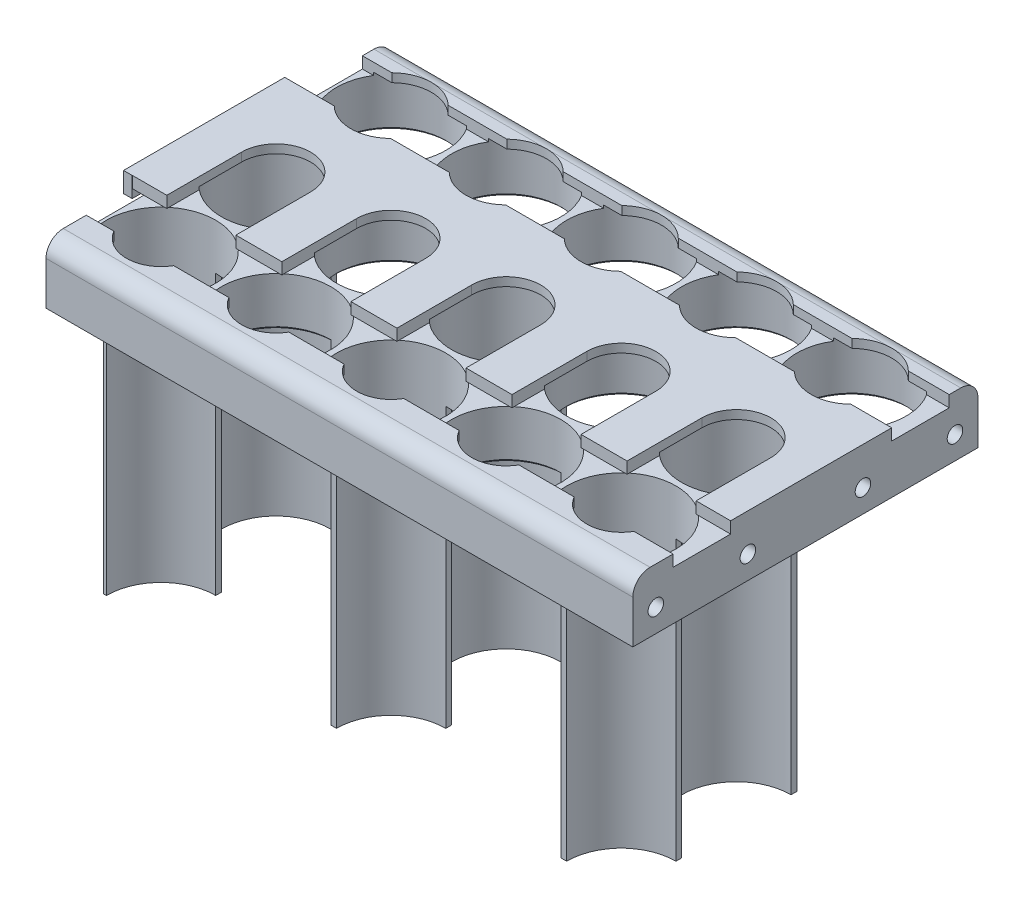
SolidWorks part; units mm, degrees
ref_plane "Front Plane" through (0, 0, 0) normal (0, 0, 1) x (1, 0, 0)
ref_plane "Top Plane" through (0, 0, 0) normal (0, 1, 0) x (1, 0, 0)
ref_plane "Right Plane" through (0, 0, 0) normal (1, 0, 0) x (0, 0, -1)
sketch "Sketch1" plane through (0, 0, 0) normal (0, 1, 0) x (1, 0, 0)
  line L0 (-48.3182, 0) -> (75.8679, 0)
  line L1 (-38.6124, 30) -> (61.3876, 30)
  line L2 (-38.6124, 30) -> (-38.6124, -30)
  line L3 (-38.6124, -30) -> (61.3876, -30)
  line L4 (61.3876, 30) -> (61.3876, -30)
  circle A0 centre (-28.6124, 20) radius 9.5
  circle A1 centre (-8.6124, 20) radius 9.5
  circle A2 centre (11.3876, 20) radius 9.5
  circle A3 centre (31.3876, 20) radius 9.5
  circle A4 centre (51.3876, 20) radius 9.5
  circle A5 centre (-28.6124, 0) radius 9.5
  circle A6 centre (-8.6124, 0) radius 9.5
  circle A7 centre (11.3876, 0) radius 9.5
  circle A8 centre (31.3876, 0) radius 9.5
  circle A9 centre (51.3876, 0) radius 9.5
  circle A10 centre (51.3876, -20) radius 9.5
  circle A11 centre (31.3876, -20) radius 9.5
  circle A12 centre (11.3876, -20) radius 9.5
  circle A13 centre (-8.6124, -20) radius 9.5
  circle A14 centre (-28.6124, -20) radius 9.5
  dimension "D3" = 19
  dimension "D4" = 19
  dimension "D5" = 19
  dimension "D6" = 19
  dimension "D7" = 19
  dimension "D8" = 20
  dimension "D9" = 20
  dimension "D10" = 20
  dimension "D11" = 20
  dimension "D12" = 10
  dimension "D13" = 10
  dimension "D14" = 20
  dimension "D15" = 20
  dimension "D16" = 20
  dimension "D17" = 20
  dimension "D18" = 20
  dimension "D19" = 10
  dimension "D20" = 20
  dimension "D21" = 20
  dimension "D22" = 20
  dimension "D23" = 20
  dimension "D25" = 30
  dimension "D26" = 19
  dimension "D27" = 19
  dimension "D28" = 19
  dimension "D29" = 19
  dimension "D30" = 19
  dimension "D1" = 60
  dimension "D2" = 100
  dimension "D24" = 10
extrude "Boss-Extrude1" add sketch "Sketch1" along normal blind 10 contours A9 L0 A8 A7 A6 A5 L2 L3 L4 A13 A11 A10 A12 A14 | A9 L0 L4 L1 L2 A5 A6 A7 A8 A4 A3 A2 A1 A0 region at (-37.5683, 0, -15) region at (-38.3624, 0, 1.044)
sketch "Sketch2" plane through (0, 10, 0) normal (0, 1, 0) x (1, 0, 0)
  line L1 (-38.6124, 30) -> (61.3876, 30)
  line L2 (-38.6124, 30) -> (-38.6124, -30)
  line L3 (-38.6124, -30) -> (61.3876, -30)
  line L4 (61.3876, 30) -> (61.3876, -30)
extrude "Boss-Extrude2" add sketch "Sketch2" against normal blind 1.5
sketch "Sketch3" plane through (0, 10, 0) normal (0, 1, 0) x (1, 0, 0)
  line L0 (-28.6124, 0) -> (-28.6124, -20) construction
  line L1 (-22.6124, 0) -> (-22.6124, -20)
  line L2 (-34.6124, 0) -> (-34.6124, -20)
  line L3 (-8.6124, 0) -> (-8.6124, -20) construction
  line L4 (-2.6124, 0) -> (-2.6124, -20)
  line L5 (-14.6124, 0) -> (-14.6124, -20)
  line L6 (11.3876, 34.8884) -> (11.3876, -40.3884)
  line L7 (61.3876, 30) -> (61.3876, -30) construction
  line L8 (31.3876, 0) -> (31.3876, -20) construction
  line L9 (25.3876, 0) -> (25.3876, -20)
  line L10 (37.3876, 0) -> (37.3876, -20)
  line L11 (51.3876, 0) -> (51.3876, -20) construction
  line L12 (45.3876, 0) -> (45.3876, -20)
  line L13 (57.3876, 0) -> (57.3876, -20)
  line L14 (11.3876, 0) -> (11.3876, -20) construction
  line L15 (17.3876, 0) -> (17.3876, -20)
  line L16 (5.3876, 0) -> (5.3876, -20)
  arc A0 (-22.6124, 0) -> (-34.6124, 0) centre (-28.6124, 0) ccw
  arc A1 (-34.6124, -20) -> (-22.6124, -20) centre (-28.6124, -20) ccw
  circle A2 centre (-28.6124, -20) radius 9.5 construction
  arc A3 (-2.6124, 0) -> (-14.6124, 0) centre (-8.6124, 0) ccw
  arc A4 (-14.6124, -20) -> (-2.6124, -20) centre (-8.6124, -20) ccw
  arc A5 (25.3876, 0) -> (37.3876, 0) centre (31.3876, 0) cw
  arc A6 (37.3876, -20) -> (25.3876, -20) centre (31.3876, -20) cw
  arc A7 (45.3876, 0) -> (57.3876, 0) centre (51.3876, 0) cw
  arc A8 (57.3876, -20) -> (45.3876, -20) centre (51.3876, -20) cw
  arc A9 (17.3876, 0) -> (5.3876, 0) centre (11.3876, 0) ccw
  arc A10 (5.3876, -20) -> (17.3876, -20) centre (11.3876, -20) ccw
  point P3 (-28.6124, -10)
  point P10 (-22.6124, -10)
  point P14 (-8.6124, -10)
  point P25 (31.3876, -10)
  point P32 (51.3876, -10)
  point P39 (11.3876, -10)
  dimension "D1" = 12
  dimension "D2" = 12
  dimension "D3" = 50
  dimension "D4" = 12
extrude "Cut-Extrude1" cut sketch "Sketch3" against normal blind 1.5 contours L5 A4 L4 A3 | L2 A1 L1 A0 | L6 A10 L15 A9 | L16 A10 L6 A9 | A8 L13 A7 L12 | A6 L10 A5 L9 region at (-28.6124, 10, 10) region at (-8.6124, 10, 10) region at (14.2424, 10, 10) region at (8.5329, 10, 10) region at (31.3876, 10, 10) region at (51.3876, 10, 10)
sketch "Sketch4" plane through (0, 10, 0) normal (0, 1, 0) x (1, 0, 0)
  line L1 (-46.445, -13) -> (66.265, -13)
  line L2 (-46.445, -13) -> (-46.445, -23)
  line L3 (-46.445, -23) -> (66.265, -23)
  line L4 (66.265, -13) -> (66.265, -23)
  arc A1 (-22.6124, -12.6345) -> (-34.6124, -12.6345) centre (-28.6124, -20) ccw construction
  arc A2 (-34.6124, -7.3655) -> (-22.6124, -7.3655) centre (-28.6124, 0) ccw construction
  dimension "D2" = 3
  dimension "D1" = 10
  dimension "D3" = 13
extrude "Cut-Extrude2" cut sketch "Sketch4" against normal blind 1.5
sketch "Sketch5" plane through (0, 10, 0) normal (0, 1, 0) x (1, 0, 0)
  line L1 (-43.2435, 25) -> (67.4964, 25)
  line L2 (-43.2435, 25) -> (-43.2435, 15)
  line L3 (-43.2435, 15) -> (67.4964, 15)
  line L4 (67.4964, 25) -> (67.4964, 15)
  line L6 (-38.6124, 30) -> (61.3876, 30) construction
  dimension "D1" = 10
  dimension "D2" = 5
extrude "Cut-Extrude4" cut sketch "Sketch5" against normal blind 1.5
sketch "Sketch6" plane through (0, 10, 0) normal (0, 1, 0) x (1, 0, 0)
  line L0 (-33.8085, -23) -> (-38.6124, -23) construction
  line L1 (-38.6124, -23) -> (-38.6124, -30) construction
  line L2 (-38.6124, -30) -> (61.3876, -30) construction
  line L3 (61.3876, -30) -> (61.3876, -23) construction
  line L4 (61.3876, -23) -> (56.5838, -23) construction
  line L5 (46.1915, -23) -> (36.5838, -23) construction
  line L6 (26.1915, -23) -> (16.5838, -23) construction
  line L7 (6.1915, -23) -> (-3.4162, -23) construction
  line L8 (-13.8085, -23) -> (-23.4162, -23) construction
  line L9 (-38.6124, 25) -> (61.3876, 25) construction
  line L10 (61.3876, 25) -> (61.3876, 30) construction
  line L11 (61.3876, 30) -> (-38.6124, 30) construction
  line L12 (-38.6124, 30) -> (-38.6124, 25) construction
  line L13 (61.3876, 15) -> (-38.6124, 15) construction
  line L14 (-38.6124, 15) -> (-38.6124, -13) construction
  line L15 (-38.6124, -13) -> (-34.6124, -13) construction
  line L16 (-34.6124, -13) -> (-34.6124, 0) construction
  line L17 (-22.6124, 0) -> (-22.6124, -13) construction
  line L18 (-22.6124, -13) -> (-14.6124, -13) construction
  line L19 (-14.6124, -13) -> (-14.6124, 0) construction
  line L20 (-2.6124, 0) -> (-2.6124, -13) construction
  line L21 (-2.6124, -13) -> (5.3876, -13) construction
  line L22 (5.3876, -13) -> (5.3876, 0) construction
  line L23 (17.3876, 0) -> (17.3876, -13) construction
  line L24 (17.3876, -13) -> (25.3876, -13) construction
  line L25 (25.3876, -13) -> (25.3876, 0) construction
  line L26 (37.3876, 0) -> (37.3876, -13) construction
  line L27 (37.3876, -13) -> (45.3876, -13) construction
  line L28 (45.3876, -13) -> (45.3876, 0) construction
  line L29 (57.3876, 0) -> (57.3876, -13) construction
  line L30 (57.3876, -13) -> (61.3876, -13) construction
  line L31 (61.3876, -13) -> (61.3876, 15) construction
  line L32 (-33.8085, -23) -> (-38.6124, -23)
  line L33 (-38.6124, -23) -> (-38.6124, -30)
  line L34 (-38.6124, -30) -> (61.3876, -30)
  line L35 (61.3876, -30) -> (61.3876, -23)
  line L36 (61.3876, -23) -> (56.5838, -23)
  line L37 (46.1915, -23) -> (36.5838, -23)
  line L38 (26.1915, -23) -> (16.5838, -23)
  line L39 (6.1915, -23) -> (-3.4162, -23)
  line L40 (-13.8085, -23) -> (-23.4162, -23)
  line L41 (-38.6124, 25) -> (61.3876, 25)
  line L42 (61.3876, 25) -> (61.3876, 30)
  line L43 (61.3876, 30) -> (-38.6124, 30)
  line L44 (-38.6124, 30) -> (-38.6124, 25)
  line L45 (61.3876, 15) -> (-38.6124, 15)
  line L46 (-38.6124, 15) -> (-38.6124, -13)
  line L47 (-38.6124, -13) -> (-34.6124, -13)
  line L48 (-34.6124, -13) -> (-34.6124, 0)
  line L49 (-22.6124, 0) -> (-22.6124, -13)
  line L50 (-22.6124, -13) -> (-14.6124, -13)
  line L51 (-14.6124, -13) -> (-14.6124, 0)
  line L52 (-2.6124, 0) -> (-2.6124, -13)
  line L53 (-2.6124, -13) -> (5.3876, -13)
  line L54 (5.3876, -13) -> (5.3876, 0)
  line L55 (17.3876, 0) -> (17.3876, -13)
  line L56 (17.3876, -13) -> (25.3876, -13)
  line L57 (25.3876, -13) -> (25.3876, 0)
  line L58 (37.3876, 0) -> (37.3876, -13)
  line L59 (37.3876, -13) -> (45.3876, -13)
  line L60 (45.3876, -13) -> (45.3876, 0)
  line L61 (57.3876, 0) -> (57.3876, -13)
  line L62 (57.3876, -13) -> (61.3876, -13)
  line L63 (61.3876, -13) -> (61.3876, 15)
  arc A0 (46.1915, -23) -> (56.5838, -23) centre (51.3876, -20) ccw construction
  arc A1 (26.1915, -23) -> (36.5838, -23) centre (31.3876, -20) ccw construction
  arc A2 (6.1915, -23) -> (16.5838, -23) centre (11.3876, -20) ccw construction
  arc A3 (-13.8085, -23) -> (-3.4162, -23) centre (-8.6124, -20) ccw construction
  arc A4 (-33.8085, -23) -> (-23.4162, -23) centre (-28.6124, -20) ccw construction
  arc A5 (-22.6124, 0) -> (-34.6124, 0) centre (-28.6124, 0) ccw construction
  arc A6 (-2.6124, 0) -> (-14.6124, 0) centre (-8.6124, 0) ccw construction
  arc A7 (17.3876, 0) -> (5.3876, 0) centre (11.3876, 0) ccw construction
  arc A8 (37.3876, 0) -> (25.3876, 0) centre (31.3876, 0) ccw construction
  arc A9 (57.3876, 0) -> (45.3876, 0) centre (51.3876, 0) ccw construction
  arc A10 (46.1915, -23) -> (56.5838, -23) centre (51.3876, -20) ccw
  arc A11 (26.1915, -23) -> (36.5838, -23) centre (31.3876, -20) ccw
  arc A12 (6.1915, -23) -> (16.5838, -23) centre (11.3876, -20) ccw
  arc A13 (-13.8085, -23) -> (-3.4162, -23) centre (-8.6124, -20) ccw
  arc A14 (-33.8085, -23) -> (-23.4162, -23) centre (-28.6124, -20) ccw
  arc A15 (-22.6124, 0) -> (-34.6124, 0) centre (-28.6124, 0) ccw
  arc A16 (-2.6124, 0) -> (-14.6124, 0) centre (-8.6124, 0) ccw
  arc A17 (17.3876, 0) -> (5.3876, 0) centre (11.3876, 0) ccw
  arc A18 (37.3876, 0) -> (25.3876, 0) centre (31.3876, 0) ccw
  arc A19 (57.3876, 0) -> (45.3876, 0) centre (51.3876, 0) ccw
extrude "Boss-Extrude3" add sketch "Sketch6" along normal blind 0.5
sketch "Sketch9" plane through (0, 0, 0) normal (0, -1, 0) x (1, 0, 0)
  line L0 (-28.6124, 20) -> (-28.6124, -0.7639)
  line L1 (31.3876, 20) -> (51.3876, 20)
  line L2 (31.3876, 20) -> (31.3876, 0)
  line L3 (31.3876, 0) -> (51.3876, 0)
  line L4 (-38.6124, -30) -> (61.3876, -30)
  line L5 (61.3876, -30) -> (61.3876, 30)
  line L6 (61.3876, 30) -> (-38.6124, 30)
  line L7 (-38.6124, 30) -> (-38.6124, -30)
  line L8 (-38.6124, -30) -> (61.3876, -30)
  line L9 (61.3876, -30) -> (61.3876, 30)
  line L10 (61.3876, 30) -> (-38.6124, 30)
  line L11 (-38.6124, 30) -> (-38.6124, -30)
  line L12 (51.3876, 20) -> (51.3876, 0)
  line L13 (-8.6124, 20) -> (11.3876, 20)
  line L14 (-8.6124, 20) -> (-8.6124, 0)
  line L15 (-8.6124, 0) -> (11.3876, 0)
  line L16 (11.3876, 20) -> (11.3876, 0)
  line L17 (-8.6124, 0) -> (11.3876, 0)
  line L18 (-8.6124, 0) -> (-8.6124, -20)
  line L19 (-8.6124, -20) -> (11.3876, -20)
  line L20 (11.3876, 0) -> (11.3876, -20)
  line L21 (31.3876, 0) -> (51.3876, 0)
  line L22 (31.3876, 0) -> (31.3876, -20)
  line L23 (31.3876, -20) -> (51.3876, -20)
  line L24 (51.3876, 0) -> (51.3876, -20)
  line L25 (-28.6124, 20) -> (-38.6582, 20)
  line L26 (-28.6124, -0.7639) -> (-38.6582, -0.7639)
  line L27 (-38.6582, 20) -> (-38.6582, -0.7639)
  line L28 (-28.6124, -20) -> (-28.6124, -0.7639)
  line L29 (-28.6124, -20) -> (-38.6582, -20)
  line L30 (-28.6124, -0.7639) -> (-38.6582, -0.7639)
  line L31 (-38.6582, -20) -> (-38.6582, -0.7639)
  circle A0 centre (11.3876, -20) radius 9.5 construction
  circle A1 centre (31.3876, -20) radius 9.5 construction
  circle A2 centre (51.3876, -20) radius 9.5 construction
  circle A3 centre (51.3876, 0) radius 9.5 construction
  circle A4 centre (31.3876, 0) radius 9.5 construction
  circle A5 centre (51.3876, 20) radius 9.5 construction
  circle A6 centre (31.3876, 20) radius 9.5 construction
  circle A7 centre (11.3876, 0) radius 9.5 construction
  circle A8 centre (11.3876, 20) radius 9.5 construction
  circle A9 centre (-8.6124, 20) radius 9.5 construction
  circle A10 centre (-8.6124, 0) radius 9.5 construction
  circle A11 centre (-8.6124, -20) radius 9.5 construction
  circle A12 centre (-28.6124, -20) radius 9.5 construction
  arc A13 (-20.5346, -15) -> (-36.6901, -15) centre (-28.6124, -20) ccw construction
  circle A14 centre (-28.6124, 0) radius 9.5 construction
  circle A15 centre (-28.6124, 20) radius 9.5 construction
  circle A16 centre (11.3876, -20) radius 9.5
  circle A17 centre (31.3876, -20) radius 9.5
  circle A18 centre (51.3876, -20) radius 9.5
  circle A19 centre (51.3876, 0) radius 9.5
  circle A20 centre (31.3876, 0) radius 9.5
  circle A21 centre (51.3876, 20) radius 9.5
  circle A22 centre (31.3876, 20) radius 9.5
  circle A23 centre (11.3876, 0) radius 9.5
  circle A24 centre (11.3876, 20) radius 9.5
  circle A25 centre (-8.6124, 20) radius 9.5
  circle A26 centre (-8.6124, 0) radius 9.5
  circle A27 centre (-8.6124, -20) radius 9.5
  circle A28 centre (-28.6124, -20) radius 9.5
  arc A29 (-20.5346, -15) -> (-36.6901, -15) centre (-28.6124, -20) ccw
  circle A30 centre (-28.6124, 0) radius 9.5
  circle A31 centre (-28.6124, 20) radius 9.5
  circle M19 centre (51.3876, 0) radius 9.5
  circle M20 centre (31.3876, 0) radius 9.5
  circle M21 centre (11.3876, 0) radius 9.5
  circle M22 centre (-8.6124, 0) radius 9.5
  circle M23 centre (-28.6124, 0) radius 9.5
  circle M24 centre (-8.6124, 20) radius 9.5
  circle M25 centre (31.3876, 20) radius 9.5
  line M29 (-38.6124, 30) -> (-38.6124, -30)
  circle M30 centre (51.3876, 20) radius 9.5
  circle M31 centre (11.3876, 20) radius 9.5
  circle M32 centre (-28.6124, 20) radius 9.5
  circle M33 centre (51.3876, -20) radius 9.5
  circle M34 centre (31.3876, -20) radius 9.5
  circle M35 centre (11.3876, -20) radius 9.5
  circle M36 centre (-8.6124, -20) radius 9.5
  circle M37 centre (-28.6124, -20) radius 9.5
  dimension "D1" = 0
extrude "Boss-Extrude6" add sketch "Sketch9" along normal blind 51 contours L20 L15 L18 L19 M21 M22 M36 M35 | L16 L13 L14 L15 M31 M24 M22 M21 | L12 L1 L2 L3 M30 M25 M20 M19 | L24 L3 L22 L23 M19 M20 M34 M33 | L29 A28 L28 L26 M37 M23 M29 | L26 L0 L25 L11 M23 M32 region at (-35.9849, 0, 9.9309) region at (-35.9529, 0, -10.0648) region at (41.3876, 0, 10) region at (41.3876, 0, -10) region at (1.3876, 0, 10) region at (1.3876, 0, -10)
sketch "Sketch10" plane through (0, 0, -30) normal (0, 0, -1) x (-1, 0, 0)
  line L0 (-61.3876, 10.5) -> (38.6124, 10.5) construction
  line L1 (-63.46, -48) -> (49.0928, -48)
  line L2 (-63.46, -48) -> (-63.46, -89.3372)
  line L3 (-63.46, -89.3372) -> (49.0928, -89.3372)
  line L4 (49.0928, -48) -> (49.0928, -89.3372)
  dimension "D1" = 58.5
extrude "Cut-Extrude5" cut sketch "Sketch10" against normal blind 66
sketch "Sketch12" plane through (0, 10.5, 0) normal (0, 1, 0) x (1, 0, 0)
  line L0 (11.3876, 36.6211) -> (11.3876, -37.2004)
  line L1 (61.3876, -13) -> (61.3876, 15) construction
  circle A0 centre (-28.6124, 20) radius 7
  circle A1 centre (-8.6124, 20) radius 7
  arc A2 (-20.5346, 15) -> (-20.5346, 25) centre (-28.6124, 20) ccw construction
  circle A3 centre (11.3876, 20) radius 7
  circle A4 centre (51.3876, 20) radius 7
  circle A5 centre (31.3876, 20) radius 7
  dimension "D1" = 14
  dimension "D2" = 14
  dimension "D4" = 14
  dimension "D3" = 50
extrude "Cut-Extrude7" cut sketch "Sketch12" against normal blind 10 contours A0 | A1 | A3 | A5 | A4
chamfer "Chamfer1" distance 0.5 angle 45 15 edges at (58.1051, 0, 26.7175) (60.8876, 0, 0) (58.1051, 0, -26.7175) (24.6701, 0, 26.7175) (18.1051, 0, 26.7175) (24.6701, 0, -26.7175) (21.8876, 0, 0) (20.8876, 0, 0) (18.1051, 0, -26.7175) (-15.3299, 0, -26.7175) (-21.8949, 0, -26.7175) (-19.1124, 0, 0) (-21.8949, 0, 26.7175) (-18.1124, 0, 0) (-15.3299, 0, 26.7175)
fillet "Fillet1" radius 3 2 edges at (11.3876, 10.5, 30) (11.3876, 10.5, -30)
sketch "Sketch13" plane through (-38.6124, 0, 0) normal (-1, 0, 0) x (0, 0, 1)
  line L1 (-15, 10.5) -> (13, 10.5)
  line L2 (-15, 10.5) -> (-15, 8.5)
  line L3 (-15, 8.5) -> (13, 8.5)
  line L4 (13, 10.5) -> (13, 8.5)
extrude "Boss-Extrude7" add sketch "Sketch13" along normal blind 2
sketch "Sketch14" plane through (-40.6124, 0, 0) normal (-1, 0, 0) x (0, 0, 1)
  line L0 (-15, 8.5) -> (13, 8.5) construction
  line L1 (-15, 10.5) -> (13.0198, 10.5)
  line L2 (-15, 10.5) -> (-15, 7)
  line L3 (-15, 7) -> (13.0198, 7)
  line L4 (13.0198, 10.5) -> (13.0198, 7)
  dimension "D1" = 1.5
extrude "Boss-Extrude8" add sketch "Sketch14" along normal blind 1.5
sketch "Sketch15" plane through (61.3876, 0, 0) normal (1, 0, 0) x (0, 0, -1)
  line L15 (-23, 10.5) -> (-27, 10.5)
  line L16 (-30, 7.5) -> (-30, 0)
  line L17 (-30, 0) -> (-20, 0)
  line L18 (-20, 0) -> (0, 0)
  line L19 (0, 0) -> (20, 0)
  line L20 (20, 0) -> (30, 0)
  line L21 (30, 0) -> (30, 7.5)
  line L22 (27, 10.5) -> (25, 10.5)
  line L23 (25, 10.5) -> (25, 8.5)
  line L24 (25, 8.5) -> (15, 8.5)
  line L25 (15, 8.5) -> (15, 10.5)
  line L26 (15, 10.5) -> (-13, 10.5)
  line L27 (-13, 10.5) -> (-13, 8.5)
  line L28 (-13, 8.5) -> (-23, 8.5)
  line L29 (-23, 8.5) -> (-23, 10.5)
  line L30 (-23, 10.5) -> (-27, 10.5)
  line L31 (-30, 7.5) -> (-30, 0)
  line L32 (-30, 0) -> (-20, 0)
  line L33 (-20, 0) -> (0, 0)
  line L34 (0, 0) -> (20, 0)
  line L35 (20, 0) -> (30, 0)
  line L36 (30, 0) -> (30, 7.5)
  line L37 (27, 10.5) -> (25, 10.5)
  line L38 (25, 10.5) -> (25, 8.5)
  line L39 (25, 8.5) -> (15, 8.5)
  line L40 (15, 8.5) -> (15, 10.5)
  line L41 (15, 10.5) -> (-13, 10.5)
  line L42 (-13, 10.5) -> (-13, 8.5)
  line L43 (-13, 8.5) -> (-23, 8.5)
  line L44 (-23, 8.5) -> (-23, 10.5)
  arc A2 (-27, 10.5) -> (-30, 7.5) centre (-27, 7.5) ccw
  arc A3 (30, 7.5) -> (27, 10.5) centre (27, 7.5) ccw
  arc A4 (-27, 10.5) -> (-30, 7.5) centre (-27, 7.5) ccw
  arc A5 (30, 7.5) -> (27, 10.5) centre (27, 7.5) ccw
  dimension "D1" = 0
extrude "Boss-Extrude9" add sketch "Sketch15" along normal blind 2
sketch "Sketch16" plane through (63.3876, 0, 0) normal (1, 0, 0) x (0, 0, -1)
  line L0 (-30, 0) -> (30, 0) construction
  line L1 (30, 0) -> (30, 7.5) construction
  line L2 (-30, 7.5) -> (-30, 0) construction
  circle A0 centre (10, 4) radius 1.35
  circle A1 centre (-10, 4) radius 1.35
  dimension "D1" = 4
  dimension "D2" = 4
  dimension "D3" = 20
  dimension "D4" = 2.7
  dimension "D5" = 2.7
  dimension "D6" = 20
extrude "Cut-Extrude8" cut sketch "Sketch16" against normal blind 5
sketch "Sketch17" plane through (63.3876, 0, 0) normal (1, 0, 0) x (0, 0, -1)
  line L0 (-30, 0) -> (30, 0) construction
  line L1 (30, 0) -> (30, 7.5) construction
  line L2 (0, 12.533) -> (0, -52.7825)
  circle A0 centre (26, 4) radius 1.35
  circle A1 centre (-26, 4) radius 1.35
  dimension "D1" = 4
  dimension "D2" = 4
  dimension "D3" = 2.7
extrude "Cut-Extrude9" cut sketch "Sketch17" against normal blind 3 contours A1 | A0 region at (63.3876, 4, -26) region at (63.3876, 4, 26)
sketch "Sketch18" plane through (0, 8.5, 0) normal (0, -1, 0) x (1, 0, 0)
  line L0 (46.4886, -25) -> (43.3099, -25) construction
  line L1 (59.4654, -25) -> (56.2866, -25) construction
  line L2 (26.4886, -25) -> (23.3099, -25) construction
  line L3 (39.4654, -25) -> (36.2866, -25) construction
  line L4 (19.4654, -25) -> (16.2866, -25) construction
  line L5 (6.4886, -25) -> (3.3099, -25) construction
  line L6 (-0.5346, -25) -> (-3.7134, -25) construction
  line L7 (-13.5114, -25) -> (-16.6901, -25) construction
  line L8 (-20.5346, -25) -> (-23.7134, -25) construction
  line L9 (-33.5114, -25) -> (-36.6901, -25) construction
  line L10 (-36.6901, -15) -> (-33.5114, -15) construction
  line L11 (-23.7134, -15) -> (-20.5346, -15) construction
  line L12 (-16.6901, -15) -> (-13.5114, -15) construction
  line L13 (-3.7134, -15) -> (-0.5346, -15) construction
  line L14 (3.3099, -15) -> (6.4886, -15) construction
  line L15 (16.2866, -15) -> (19.4654, -15) construction
  line L16 (36.2866, -15) -> (39.4654, -15) construction
  line L17 (23.3099, -15) -> (26.4886, -15) construction
  line L18 (56.2866, -15) -> (59.4654, -15) construction
  line L19 (43.3099, -15) -> (46.4886, -15) construction
  line L20 (45.3876, 0) -> (45.3876, 7.3655) construction
  line L21 (57.3876, 7.3655) -> (57.3876, 0) construction
  line L22 (25.3876, 0) -> (25.3876, 7.3655) construction
  line L23 (37.3876, 7.3655) -> (37.3876, 0) construction
  line L24 (17.3876, 7.3655) -> (17.3876, 0) construction
  line L25 (5.3876, 0) -> (5.3876, 7.3655) construction
  line L26 (-14.6124, 0) -> (-14.6124, 7.3655) construction
  line L27 (-2.6124, 7.3655) -> (-2.6124, 0) construction
  line L28 (-34.6124, 0) -> (-34.6124, 7.3655) construction
  line L29 (-22.6124, 7.3655) -> (-22.6124, 0) construction
  line L30 (-37.6263, 23) -> (-33.8085, 23) construction
  line L31 (-23.4162, 23) -> (-19.5985, 23) construction
  line L32 (-17.6263, 23) -> (-13.8085, 23) construction
  line L33 (-3.4162, 23) -> (0.4015, 23) construction
  line L34 (2.3737, 23) -> (6.1915, 23) construction
  line L35 (16.5838, 23) -> (20.4015, 23) construction
  line L36 (42.3737, 23) -> (46.1915, 23) construction
  line L37 (56.5838, 23) -> (60.4015, 23) construction
  line L38 (22.3737, 23) -> (26.1915, 23) construction
  line L39 (36.5838, 23) -> (40.4015, 23) construction
  line L40 (46.4886, -25) -> (43.3099, -25)
  line L41 (59.4654, -25) -> (56.2866, -25)
  line L42 (26.4886, -25) -> (23.3099, -25)
  line L43 (39.4654, -25) -> (36.2866, -25)
  line L44 (19.4654, -25) -> (16.2866, -25)
  line L45 (6.4886, -25) -> (3.3099, -25)
  line L46 (-0.5346, -25) -> (-3.7134, -25)
  line L47 (-13.5114, -25) -> (-16.6901, -25)
  line L48 (-20.5346, -25) -> (-23.7134, -25)
  line L49 (-33.5114, -25) -> (-36.6901, -25)
  line L50 (-36.6901, -15) -> (-33.5114, -15)
  line L51 (-23.7134, -15) -> (-20.5346, -15)
  line L52 (-16.6901, -15) -> (-13.5114, -15)
  line L53 (-3.7134, -15) -> (-0.5346, -15)
  line L54 (3.3099, -15) -> (6.4886, -15)
  line L55 (16.2866, -15) -> (19.4654, -15)
  line L56 (36.2866, -15) -> (39.4654, -15)
  line L57 (23.3099, -15) -> (26.4886, -15)
  line L58 (56.2866, -15) -> (59.4654, -15)
  line L59 (43.3099, -15) -> (46.4886, -15)
  line L60 (45.3876, 0) -> (45.3876, 7.3655)
  line L61 (57.3876, 7.3655) -> (57.3876, 0)
  line L62 (25.3876, 0) -> (25.3876, 7.3655)
  line L63 (37.3876, 7.3655) -> (37.3876, 0)
  line L64 (17.3876, 7.3655) -> (17.3876, 0)
  line L65 (5.3876, 0) -> (5.3876, 7.3655)
  line L66 (-14.6124, 0) -> (-14.6124, 7.3655)
  line L67 (-2.6124, 7.3655) -> (-2.6124, 0)
  line L68 (-34.6124, 0) -> (-34.6124, 7.3655)
  line L69 (-22.6124, 7.3655) -> (-22.6124, 0)
  line L70 (-37.6263, 23) -> (-33.8085, 23)
  line L71 (-23.4162, 23) -> (-19.5985, 23)
  line L72 (-17.6263, 23) -> (-13.8085, 23)
  line L73 (-3.4162, 23) -> (0.4015, 23)
  line L74 (2.3737, 23) -> (6.1915, 23)
  line L75 (16.5838, 23) -> (20.4015, 23)
  line L76 (42.3737, 23) -> (46.1915, 23)
  line L77 (56.5838, 23) -> (60.4015, 23)
  line L78 (22.3737, 23) -> (26.1915, 23)
  line L79 (36.5838, 23) -> (40.4015, 23)
  arc A0 (46.4886, -25) -> (56.2866, -25) centre (51.3876, -20) ccw construction
  arc A1 (43.3099, -25) -> (59.4654, -25) centre (51.3876, -20) ccw construction
  arc A2 (26.4886, -25) -> (36.2866, -25) centre (31.3876, -20) ccw construction
  arc A3 (23.3099, -25) -> (39.4654, -25) centre (31.3876, -20) ccw construction
  arc A4 (6.4886, -25) -> (16.2866, -25) centre (11.3876, -20) ccw construction
  arc A5 (3.3099, -25) -> (19.4654, -25) centre (11.3876, -20) ccw construction
  arc A6 (-13.5114, -25) -> (-3.7134, -25) centre (-8.6124, -20) ccw construction
  arc A7 (-16.6901, -25) -> (-0.5346, -25) centre (-8.6124, -20) ccw construction
  arc A8 (-33.5114, -25) -> (-23.7134, -25) centre (-28.6124, -20) ccw construction
  arc A9 (-36.6901, -25) -> (-20.5346, -25) centre (-28.6124, -20) ccw construction
  arc A10 (-23.7134, -15) -> (-33.5114, -15) centre (-28.6124, -20) ccw construction
  arc A11 (-20.5346, -15) -> (-36.6901, -15) centre (-28.6124, -20) ccw construction
  arc A12 (-3.7134, -15) -> (-13.5114, -15) centre (-8.6124, -20) ccw construction
  arc A13 (-0.5346, -15) -> (-16.6901, -15) centre (-8.6124, -20) ccw construction
  arc A14 (16.2866, -15) -> (6.4886, -15) centre (11.3876, -20) ccw construction
  arc A15 (19.4654, -15) -> (3.3099, -15) centre (11.3876, -20) ccw construction
  arc A16 (36.2866, -15) -> (26.4886, -15) centre (31.3876, -20) ccw construction
  arc A17 (39.4654, -15) -> (23.3099, -15) centre (31.3876, -20) ccw construction
  arc A18 (56.2866, -15) -> (46.4886, -15) centre (51.3876, -20) ccw construction
  arc A19 (59.4654, -15) -> (43.3099, -15) centre (51.3876, -20) ccw construction
  arc A20 (45.3876, 0) -> (57.3876, 0) centre (51.3876, 0) ccw construction
  arc A21 (45.3876, 7.3655) -> (57.3876, 7.3655) centre (51.3876, 0) ccw construction
  arc A22 (25.3876, 0) -> (37.3876, 0) centre (31.3876, 0) ccw construction
  arc A23 (25.3876, 7.3655) -> (37.3876, 7.3655) centre (31.3876, 0) ccw construction
  arc A24 (5.3876, 0) -> (17.3876, 0) centre (11.3876, 0) ccw construction
  arc A25 (5.3876, 7.3655) -> (17.3876, 7.3655) centre (11.3876, 0) ccw construction
  arc A26 (-14.6124, 0) -> (-2.6124, 0) centre (-8.6124, 0) ccw construction
  arc A27 (-14.6124, 7.3655) -> (-2.6124, 7.3655) centre (-8.6124, 0) ccw construction
  arc A28 (-34.6124, 0) -> (-22.6124, 0) centre (-28.6124, 0) ccw construction
  arc A29 (-34.6124, 7.3655) -> (-22.6124, 7.3655) centre (-28.6124, 0) ccw construction
  arc A30 (-19.5985, 23) -> (-37.6263, 23) centre (-28.6124, 20) ccw construction
  arc A31 (-23.4162, 23) -> (-33.8085, 23) centre (-28.6124, 20) ccw construction
  arc A32 (0.4015, 23) -> (-17.6263, 23) centre (-8.6124, 20) ccw construction
  arc A33 (-3.4162, 23) -> (-13.8085, 23) centre (-8.6124, 20) ccw construction
  arc A34 (20.4015, 23) -> (2.3737, 23) centre (11.3876, 20) ccw construction
  arc A35 (16.5838, 23) -> (6.1915, 23) centre (11.3876, 20) ccw construction
  arc A36 (60.4015, 23) -> (42.3737, 23) centre (51.3876, 20) ccw construction
  arc A37 (56.5838, 23) -> (46.1915, 23) centre (51.3876, 20) ccw construction
  arc A38 (40.4015, 23) -> (22.3737, 23) centre (31.3876, 20) ccw construction
  arc A39 (36.5838, 23) -> (26.1915, 23) centre (31.3876, 20) ccw construction
  arc A40 (46.4886, -25) -> (56.2866, -25) centre (51.3876, -20) ccw
  arc A41 (43.3099, -25) -> (59.4654, -25) centre (51.3876, -20) ccw
  arc A42 (26.4886, -25) -> (36.2866, -25) centre (31.3876, -20) ccw
  arc A43 (23.3099, -25) -> (39.4654, -25) centre (31.3876, -20) ccw
  arc A44 (6.4886, -25) -> (16.2866, -25) centre (11.3876, -20) ccw
  arc A45 (3.3099, -25) -> (19.4654, -25) centre (11.3876, -20) ccw
  arc A46 (-13.5114, -25) -> (-3.7134, -25) centre (-8.6124, -20) ccw
  arc A47 (-16.6901, -25) -> (-0.5346, -25) centre (-8.6124, -20) ccw
  arc A48 (-33.5114, -25) -> (-23.7134, -25) centre (-28.6124, -20) ccw
  arc A49 (-36.6901, -25) -> (-20.5346, -25) centre (-28.6124, -20) ccw
  arc A50 (-23.7134, -15) -> (-33.5114, -15) centre (-28.6124, -20) ccw
  arc A51 (-20.5346, -15) -> (-36.6901, -15) centre (-28.6124, -20) ccw
  arc A52 (-3.7134, -15) -> (-13.5114, -15) centre (-8.6124, -20) ccw
  arc A53 (-0.5346, -15) -> (-16.6901, -15) centre (-8.6124, -20) ccw
  arc A54 (16.2866, -15) -> (6.4886, -15) centre (11.3876, -20) ccw
  arc A55 (19.4654, -15) -> (3.3099, -15) centre (11.3876, -20) ccw
  arc A56 (36.2866, -15) -> (26.4886, -15) centre (31.3876, -20) ccw
  arc A57 (39.4654, -15) -> (23.3099, -15) centre (31.3876, -20) ccw
  arc A58 (56.2866, -15) -> (46.4886, -15) centre (51.3876, -20) ccw
  arc A59 (59.4654, -15) -> (43.3099, -15) centre (51.3876, -20) ccw
  arc A60 (45.3876, 0) -> (57.3876, 0) centre (51.3876, 0) ccw
  arc A61 (45.3876, 7.3655) -> (57.3876, 7.3655) centre (51.3876, 0) ccw
  arc A62 (25.3876, 0) -> (37.3876, 0) centre (31.3876, 0) ccw
  arc A63 (25.3876, 7.3655) -> (37.3876, 7.3655) centre (31.3876, 0) ccw
  arc A64 (5.3876, 0) -> (17.3876, 0) centre (11.3876, 0) ccw
  arc A65 (5.3876, 7.3655) -> (17.3876, 7.3655) centre (11.3876, 0) ccw
  arc A66 (-14.6124, 0) -> (-2.6124, 0) centre (-8.6124, 0) ccw
  arc A67 (-14.6124, 7.3655) -> (-2.6124, 7.3655) centre (-8.6124, 0) ccw
  arc A68 (-34.6124, 0) -> (-22.6124, 0) centre (-28.6124, 0) ccw
  arc A69 (-34.6124, 7.3655) -> (-22.6124, 7.3655) centre (-28.6124, 0) ccw
  arc A70 (-19.5985, 23) -> (-37.6263, 23) centre (-28.6124, 20) ccw
  arc A71 (-23.4162, 23) -> (-33.8085, 23) centre (-28.6124, 20) ccw
  arc A72 (0.4015, 23) -> (-17.6263, 23) centre (-8.6124, 20) ccw
  arc A73 (-3.4162, 23) -> (-13.8085, 23) centre (-8.6124, 20) ccw
  arc A74 (20.4015, 23) -> (2.3737, 23) centre (11.3876, 20) ccw
  arc A75 (16.5838, 23) -> (6.1915, 23) centre (11.3876, 20) ccw
  arc A76 (60.4015, 23) -> (42.3737, 23) centre (51.3876, 20) ccw
  arc A77 (56.5838, 23) -> (46.1915, 23) centre (51.3876, 20) ccw
  arc A78 (40.4015, 23) -> (22.3737, 23) centre (31.3876, 20) ccw
  arc A79 (36.5838, 23) -> (26.1915, 23) centre (31.3876, 20) ccw
extrude "Cut-Extrude10" cut sketch "Sketch18" against normal blind 0.5
sketch "Sketch20" plane through (0, -48, 0) normal (0, -1, 0) x (1, 0, 0)
  circle A0 centre (-36.1124, 10) radius 1.35
  circle A1 centre (-36.1124, -10) radius 1.35
  circle A2 centre (1.3876, 10) radius 1.35
  circle A3 centre (1.3876, -10) radius 1.35
  circle A4 centre (41.3876, -10) radius 1.35
  circle A5 centre (41.3876, 10) radius 1.35
  dimension "D1" = 2.7
  dimension "D2" = 2.7
  dimension "D3" = 2.7
  dimension "D4" = 2.7
  dimension "D5" = 2.7
  dimension "D6" = 2.7
extrude "Cut-Extrude11" cut sketch "Sketch20" against normal blind 8
